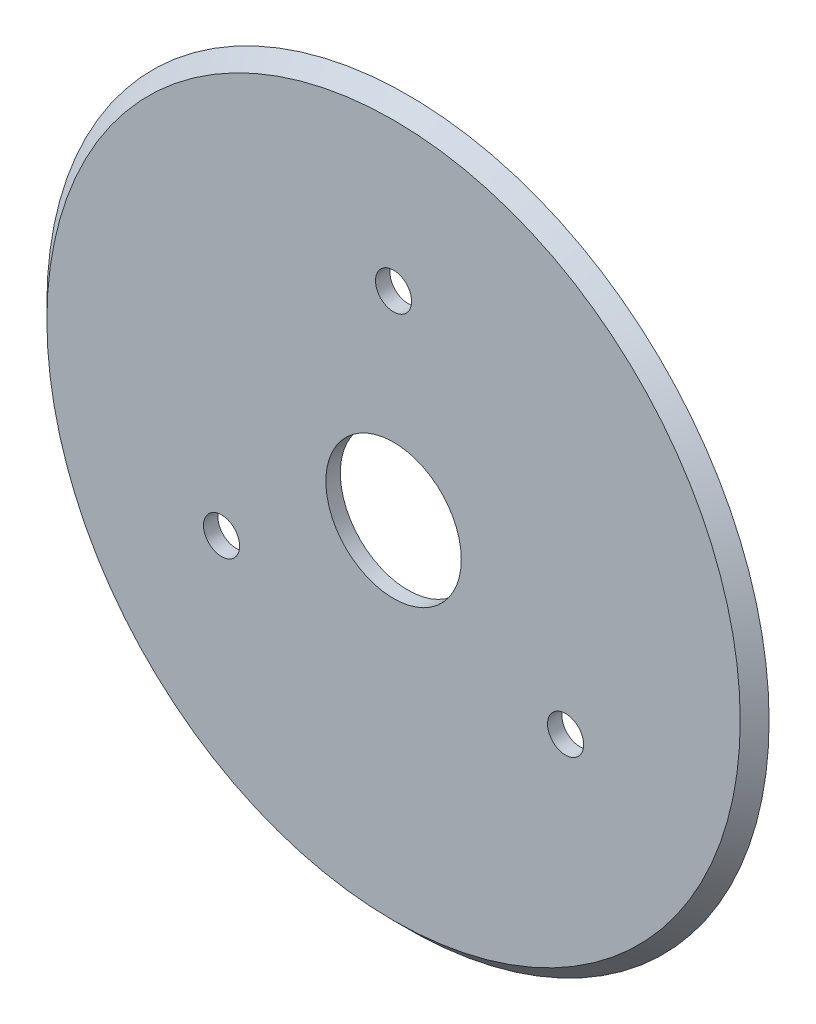
SolidWorks part; units mm, degrees
ref_plane "Front Plane" through (0, 0, 0) normal (0, 0, 1) x (1, 0, 0)
ref_plane "Top Plane" through (0, 0, 0) normal (0, 1, 0) x (1, 0, 0)
ref_plane "Right Plane" through (0, 0, 0) normal (1, 0, 0) x (0, 0, -1)
sketch "Sketch1" plane through (0, 0, 0) normal (0, 0, 1) x (1, 0, 0)
  circle A0 centre (0, 0) radius 40
  dimension "D1" = 80
extrude "Boss-Extrude1" add sketch "Sketch1" along normal blind 1.6
sketch "Sketch2" plane through (0, 0, 1.6) normal (0, 0, 1) x (1, 0, 0)
  circle A0 centre (0, 0) radius 7.5
  circle A1 centre (0, 22) radius 2
  circle A2 centre (19.0526, -11) radius 2
  circle A3 centre (-19.0526, -11) radius 2
  point P12 (0, 0)
  dimension "D1" = 15
  dimension "D2" = 4
  dimension "D3" = 22
  dimension "D4" = 3
extrude "Cut-Extrude1" cut sketch "Sketch2" against normal blind 1.6
chamfer "Chamfer1" distance 1.6 angle 45 1 edges at (40, 0, 1.6)
